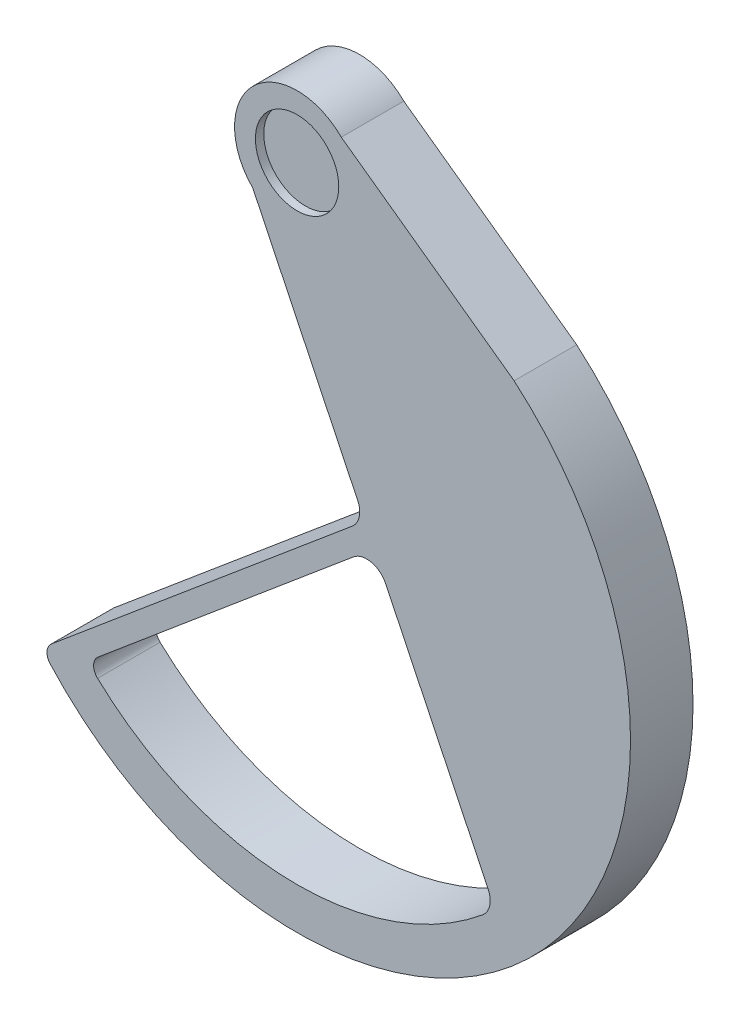
SolidWorks part; units mm, degrees
ref_plane "正面" through (0, 0, 0) normal (0, 0, 1) x (1, 0, 0)
ref_plane "平面" through (0, 0, 0) normal (0, 1, 0) x (1, 0, 0)
ref_plane "右側面" through (0, 0, 0) normal (1, 0, 0) x (0, 0, -1)
sketch "ｽｹｯﾁ4" plane through (0, 0, 0) normal (0, 0, 1) x (1, 0, 0)
  line L0 (0, 0.7897) -> (0, 0)
  line L1 (-53.6231, -124.9951) -> (-58.9406, -129.4571)
  line L3 (-10.6066, -10.6066) -> (14.5363, -62.8896)
  line L4 (-53.6231, -124.9951) -> (13.2442, -68.8868)
  line L5 (21.2324, -76.8138) -> (45.8448, -127.9938)
  line L6 (10.6066, 10.6066) -> (52.0762, -19.2705)
  line L7 (-58.0696, -135.2532) -> (-57.9498, -135.1527)
  line L8 (-47.7477, -126.5866) -> (13.5112, -75.1515)
  arc A1 (-59.2335, -133.7716) -> (52.0762, -19.2705) centre (0, -80) ccw
  arc A2 (-47.8702, -131.073) -> (44.5187, -134.0193) centre (0, -80) ccw
  arc A3 (10.6066, 10.6066) -> (-10.6066, -10.6066) centre (0, 0) ccw
  arc A4 (-59.2335, -133.7716) -> (-58.9406, -129.4571) centre (-57.0123, -131.7552) cw
  arc A5 (-47.8702, -131.073) -> (-47.7477, -126.5866) centre (-45.8186, -128.8841) cw
  arc A6 (13.5112, -75.1515) -> (21.2324, -76.8138) centre (16.7264, -78.9807) cw
  arc A7 (13.2442, -68.8868) -> (14.5363, -62.8896) centre (10.0302, -65.0566) ccw
  arc A8 (45.8448, -127.9938) -> (44.5187, -134.0193) centre (41.3388, -130.1608) cw
  point P18 (-61.2836, -131.423)
  point P21 (-50.2744, -128.7081)
  point P24 (18.4421, -71.0114)
  dimension "D3" = 140
  dimension "D4" = 30
  dimension "D5" = 5
  dimension "D6" = 3
  dimension "D7" = 3
  dimension "D8" = 5
  dimension "D9" = 5
  dimension "D10" = 5
  dimension "D2" = 5
extrude "ﾎﾞｽ - 押し出し1" add sketch "ｽｹｯﾁ4" along normal blind 15 contours A7 L4 L1 A4 A1 L6 A3 L3 L5 A8 A2 A5 L8 A6 region at (29.7837, -70.5076, 0)
sketch "ｽｹｯﾁ5" plane through (0, 0, 15) normal (0, 0, 1) x (1, 0, 0)
  circle A0 centre (0, 0) radius 10
  dimension "D1" = 20
extrude "ｶｯﾄ - 押し出し2" cut sketch "ｽｹｯﾁ5" against normal blind 2
